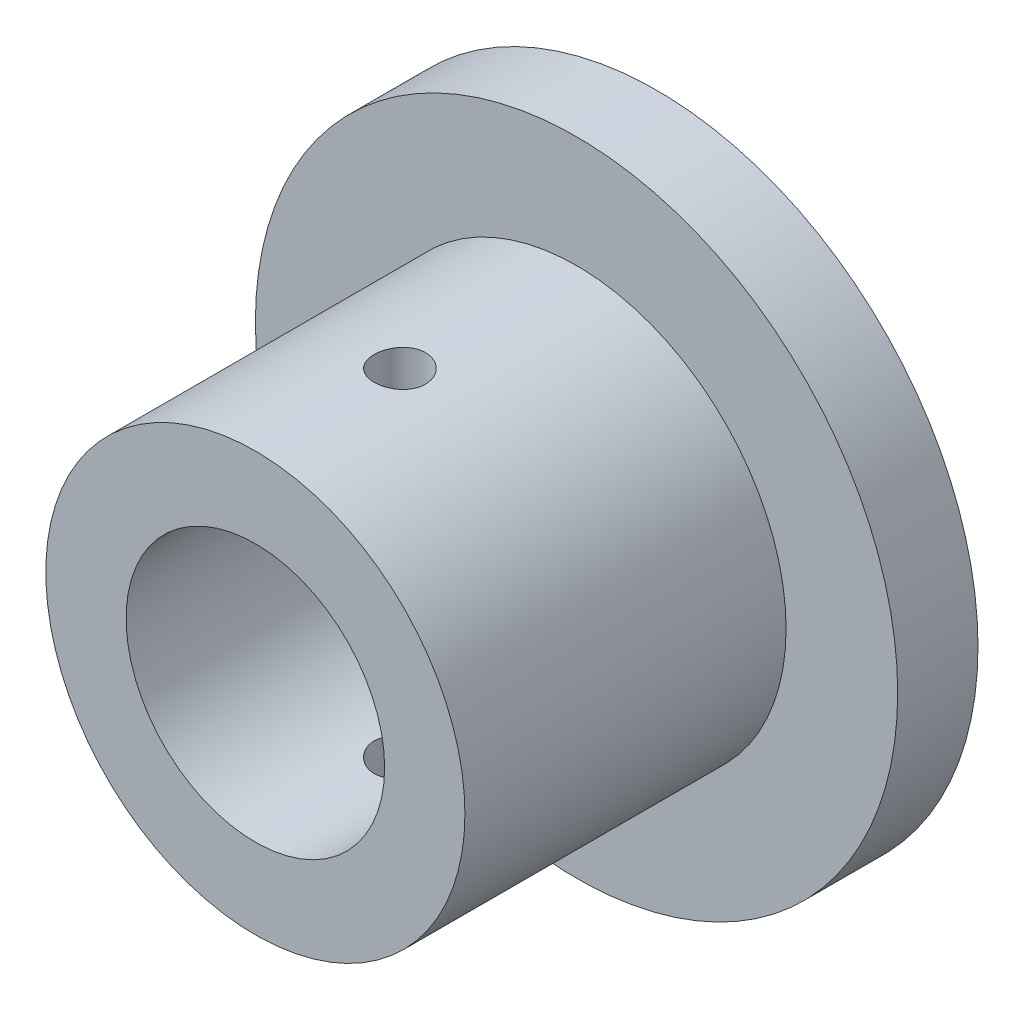
SolidWorks part; units mm, degrees
ref_plane "Alzado" through (0, 0, 0) normal (0, 0, 1) x (1, 0, 0)
ref_plane "Planta" through (0, 0, 0) normal (0, 1, 0) x (1, 0, 0)
ref_plane "Vista lateral" through (0, 0, 0) normal (1, 0, 0) x (0, 0, -1)
sketch "Croquis1" plane through (0, 0, 0) normal (0, 0, 1) x (1, 0, 0)
  circle A0 centre (0, 0) radius 20
  dimension "D1" = 40
extrude "Saliente-Extruir1" add sketch "Croquis1" along normal blind 5
sketch "Croquis2" plane through (0, 0, 5) normal (0, 0, 1) x (1, 0, 0)
  circle A0 centre (0, 0) radius 13.05
  circle A1 centre (0, 0) radius 8.05
  dimension "D2" = 16.1
  dimension "D1" = 5
extrude "Saliente-Extruir2" add sketch "Croquis2" along normal blind 20
sketch "Croquis3" plane through (0, 0, 0) normal (0, 1, 0) x (1, 0, 0)
  line L0 (-13.05, -25) -> (13.05, -25) construction
  line L1 (0, 0) -> (0, -16) construction
  circle A0 centre (0, -16) radius 1.6
  dimension "D1" = 3.2
  dimension "D2" = 9
extrude "Cortar-Extruir1" cut sketch "Croquis3" against normal mid plane 40
